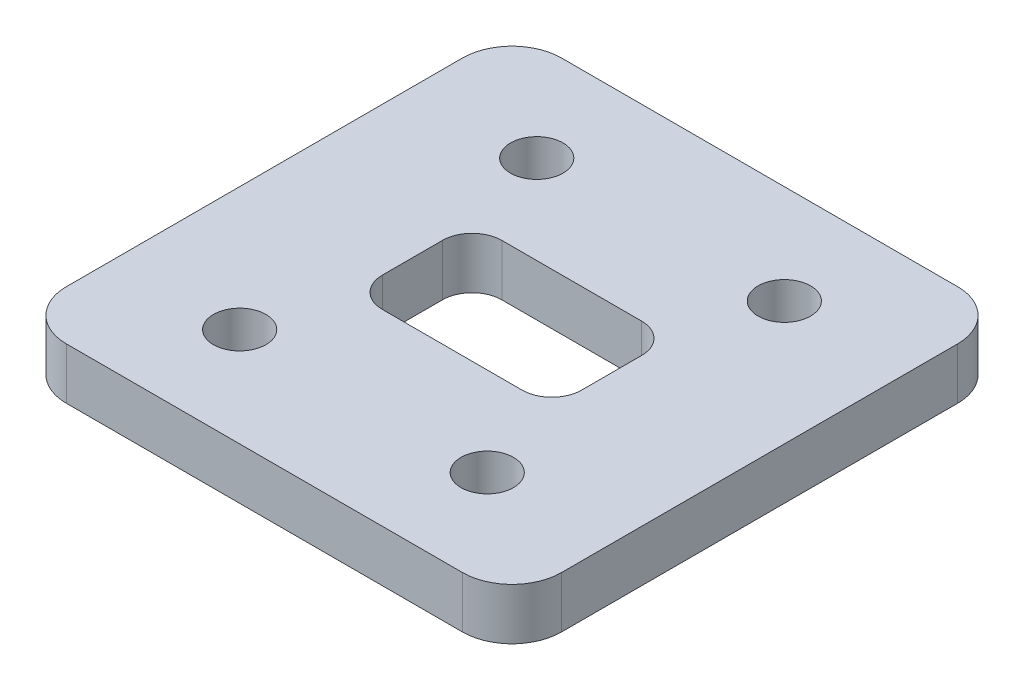
SolidWorks part; units mm, degrees
ref_plane "Alzado" through (0, 0, 0) normal (0, 0, 1) x (1, 0, 0)
ref_plane "Planta" through (0, 0, 0) normal (0, 1, 0) x (1, 0, 0)
ref_plane "Vista lateral" through (0, 0, 0) normal (1, 0, 0) x (0, 0, -1)
sketch "Croquis1" plane through (0, 0, 0) normal (0, 1, 0) x (1, 0, 0)
  line L0 (-20, -25) -> (20, -25)
  line L2 (-25, -20) -> (-25, 20)
  line L4 (25, -20) -> (25, 20)
  line L5 (-25, -25) -> (25, 25) construction
  line L6 (-25, 25) -> (25, -25) construction
  line L7 (-12.5, 15) -> (-12.5, -15) construction
  line L8 (-7.0602, -6.0357) -> (7.0602, -6.0357)
  line L9 (-20, 25) -> (20, 25)
  line L10 (-10.0602, -3.0357) -> (-10.0602, 3.0357)
  line L11 (-7.0602, 6.0357) -> (7.0602, 6.0357)
  line L12 (10.0602, -3.0357) -> (10.0602, 3.0357)
  line L13 (-12.5, 15) -> (12.5, 15) construction
  line L15 (-12.5, -15) -> (12.5, -15) construction
  line L16 (12.5, 15) -> (12.5, -15) construction
  circle A1 centre (-12.5, -15) radius 2.65
  circle A3 centre (-12.5, 15) radius 2.65
  circle A5 centre (12.5, -15) radius 2.65
  circle A8 centre (12.5, 15) radius 2.65
  arc A10 (-7.0602, -6.0357) -> (-10.0602, -3.0357) centre (-7.0602, -3.0357) cw
  arc A11 (7.0602, -6.0357) -> (10.0602, -3.0357) centre (7.0602, -3.0357) ccw
  arc A12 (10.0602, 3.0357) -> (7.0602, 6.0357) centre (7.0602, 3.0357) ccw
  arc A13 (-10.0602, 3.0357) -> (-7.0602, 6.0357) centre (-7.0602, 3.0357) cw
  arc A14 (-20, -25) -> (-25, -20) centre (-20, -20) cw
  arc A15 (25, -20) -> (20, -25) centre (20, -20) cw
  arc A16 (25, 20) -> (20, 25) centre (20, 20) ccw
  arc A17 (-25, 20) -> (-20, 25) centre (-20, 20) cw
  point P0 (0, 0)
  point P7 (0, 0)
  point P8 (0, 6.0357)
  point P12 (-10.0602, 0)
  point P14 (-12.5, 0)
  point P15 (25, 0)
  point P18 (0, 15)
  point P19 (0, 25)
  dimension "D2" = 5.3
  dimension "D3" = 30
  dimension "D4" = 5.3
  dimension "D5" = 25
  dimension "D6" = 3
  dimension "D7" = 5
  dimension "D8" = 5.3
  dimension "D9" = 5.3
  dimension "D10" = 14.1204
  dimension "D11" = 6.0713
  dimension "D12" = 40
  dimension "D13" = 40
extrude "Saliente-Extruir2" add sketch "Croquis1" along normal blind 8 contours L9 L2 L0 L4 L10 A13 L11 A12 L12 A11 L8 A10 | A1 | A3 | A8 | A5 region at (-23.0355, 0, 23.0355)
extrude "Cortar-Extruir1" cut sketch "Croquis1<4>" against normal blind 2.8 from surface contours A1 | A3 | A8 | A5 region at (-23.0355, 0, 23.0355) starting at face at (0, 8, 0)
sketch "Croquis1<4>" plane through (0, 0, 0) normal (0, 1, 0) x (1, 0, 0) same geometry as "Croquis1"
